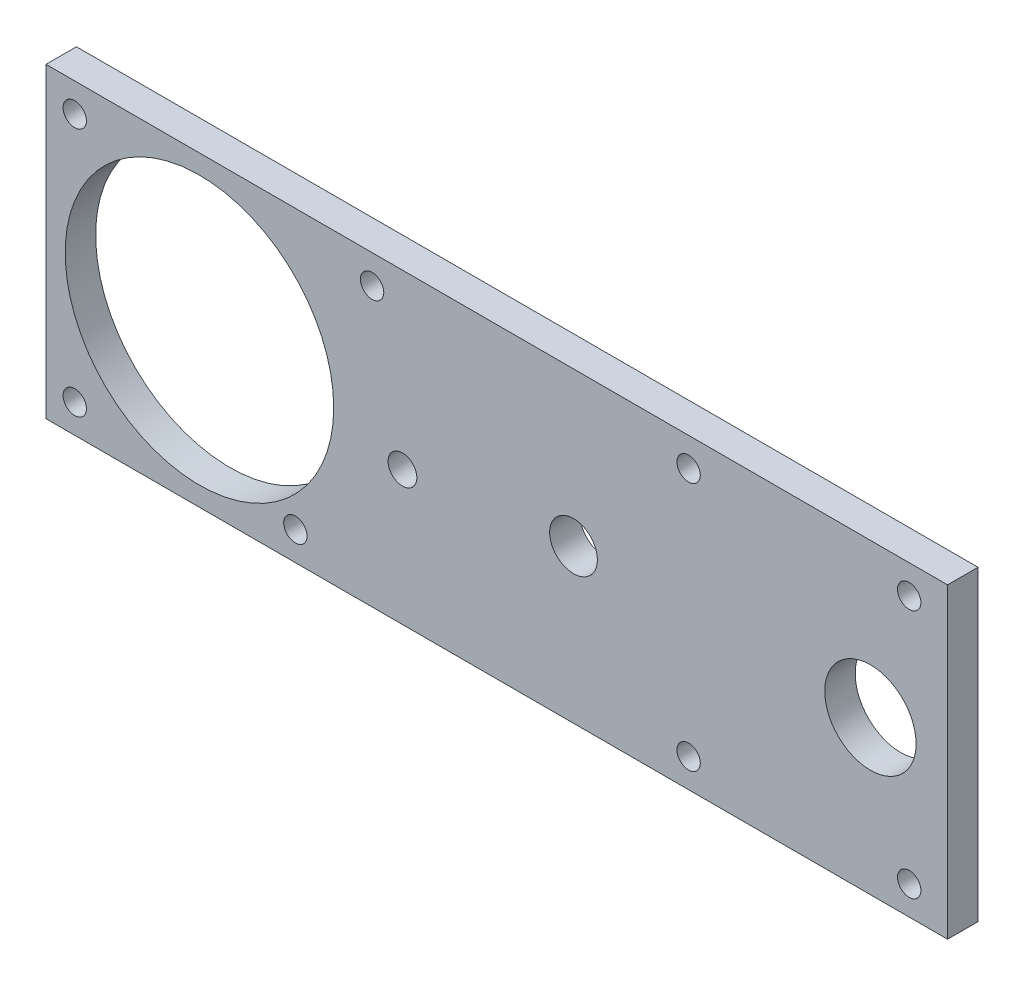
SolidWorks part; units mm, degrees
ref_plane "Front Plane" through (0, 0, 0) normal (0, 0, 1) x (1, 0, 0)
ref_plane "Top Plane" through (0, 0, 0) normal (0, 1, 0) x (1, 0, 0)
ref_plane "Right Plane" through (0, 0, 0) normal (1, 0, 0) x (0, 0, -1)
sketch "Sketch1" plane through (0, 0, 0) normal (0, 0, 1) x (1, 0, 0)
  line L0 (94, 16) -> (0, 16) construction
  line L1 (0, 0) -> (94, 0)
  line L2 (0, 0) -> (0, 32)
  line L3 (0, 32) -> (94, 32)
  line L4 (94, 0) -> (94, 32)
  circle A0 centre (55, 16) radius 2.4892
  circle A1 centre (37.1667, 14) radius 1.4986
  circle A2 centre (25.1698, 21.9334) radius 0.9906 construction
  circle A3 centre (37.1667, 14) radius 11.4777 construction
  circle A4 centre (25.1698, 21.9334) radius 7.1501 construction
  circle A5 centre (55, 16) radius 12.827 construction
  circle A6 centre (16, 16) radius 14
  circle A7 centre (37.1667, 14) radius 5.1181 construction
  point P7 (55, 16)
  point P8 (37.1667, 14)
  point P9 (25.1698, 21.9334)
  point P19 (16, 16)
  dimension "D6" = 4.9784
  dimension "D7" = 2.9972
  dimension "D8" = 1.9812
  dimension "D9" = 25.654
  dimension "D10" = 22.9553
  dimension "D11" = 14.3002
  dimension "D13" = 28
  dimension "D14" = 10.2362
  dimension "D1" = 17.9451
  dimension "D2" = 14.3828
  dimension "D3" = 32
  dimension "D4" = 94
  dimension "D5" = 55
  dimension "D12" = 10.922
  dimension "D15" = 16
  dimension "D16" = 14
extrude "Boss-Extrude2" add sketch "Sketch1" along normal blind 3.175
hole_wizard "#2 Clearance Hole1" positions "Sketch4" profile "Sketch3" hole size "#2" standard "ANSI Inch" end condition through all
sketch "Sketch4" plane through (0, 0, 3.175) normal (0, 0, 1) x (1, 0, 0)
  line L0 (90, 0) -> (90, 32) construction
  line L1 (0, 0) -> (94, 0) construction
  line L2 (94, 32) -> (0, 32) construction
  line L5 (3, 32) -> (3, 0) construction
  line L7 (0, 32) -> (0, 0) construction
  line L8 (34, 32) -> (34, 0) construction
  line L9 (3, 3) -> (90, 3) construction
  line L10 (3, 29) -> (90, 29) construction
  line L11 (67, 29) -> (67, 3) construction
  point P8 (90, 3)
  point P10 (90, 29)
  point P27 (3, 29)
  point P29 (3, 3)
  point P34 (34, 29)
  point P36 (26, 3)
  point P42 (67, 3)
  point P47 (67, 29)
  dimension "D2" = 67
  dimension "D3" = 3
  dimension "D4" = 3
  dimension "D5" = 3
  dimension "D6" = 3
  dimension "D7" = 34
  dimension "D8" = 3
  dimension "D9" = 90
  dimension "D10" = 8
sketch "Sketch3" plane through (90, 3, 3.175) normal (1, 0, 0) x (0, -1, 0)
  line L0 (0, 0) -> (0, 3.175)
  line L1 (0, 3.175) -> (1.2192, 3.175)
  line L2 (1.2192, 3.175) -> (1.2192, 0)
  line L5 (1.2192, 0) -> (0, 0)
  line L11 (0, -6.35) -> (0, 107.95) construction
  dimension "Thru Hole Dia." = 2.4384
  dimension "Thru Hole Depth" = 3.175
sketch "Sketch5" plane through (0, 0, 3.175) normal (0, 0, 1) x (1, 0, 0)
  line L0 (0, 16) -> (94, 16) construction
  line L1 (0, 32) -> (0, 0) construction
  line L2 (94, 0) -> (94, 32) construction
  circle A0 centre (85.9562, 16) radius 4.7625
  circle A1 centre (55, 16) radius 2.4892 construction
  dimension "D1" = 30.9562
  dimension "D2" = 9.525
extrude "Cut-Extrude1" cut sketch "Sketch5" against normal through all
